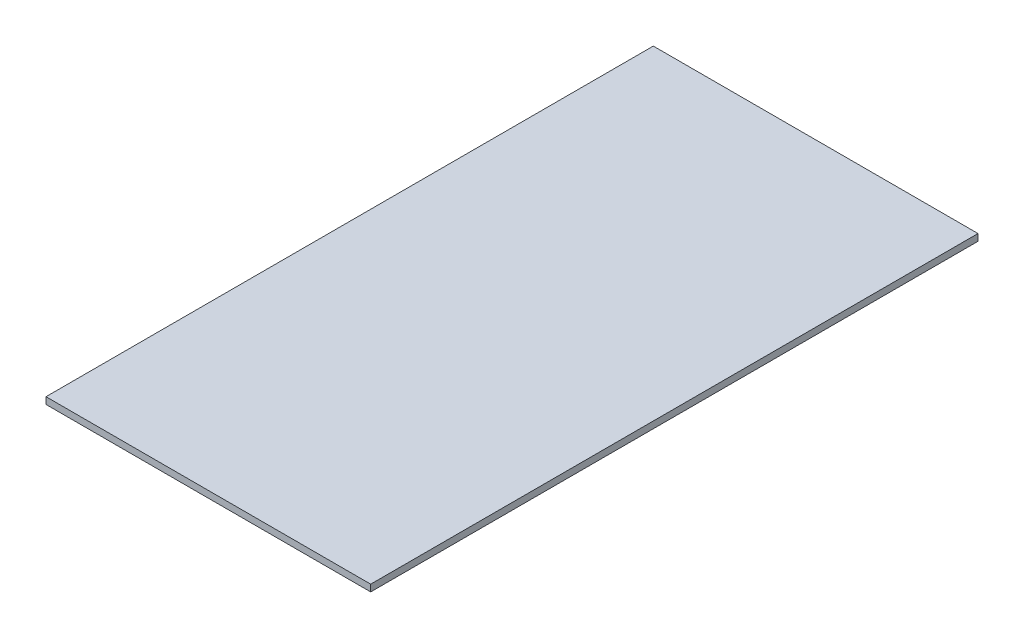
SolidWorks part; units mm, degrees
ref_plane "Front Plane" through (0, 0, 0) normal (0, 0, 1) x (1, 0, 0)
ref_plane "Top Plane" through (0, 0, 0) normal (0, 1, 0) x (1, 0, 0)
ref_plane "Right Plane" through (0, 0, 0) normal (1, 0, 0) x (0, 0, -1)
sketch "Sketch1" plane through (0, 0, 0) normal (0, 1, 0) x (1, 0, 0)
  line L1 (-53.6877, -105.9463) -> (42.5458, -105.9463)
  line L2 (-53.6877, -105.9463) -> (-53.6877, 74.0537)
  line L3 (-53.6877, 74.0537) -> (42.5458, 74.0537)
  line L4 (42.5458, -105.9463) -> (42.5458, 74.0537)
  dimension "D2" = 180
extrude "Boss-Extrude1" add sketch "Sketch1" along normal blind 2
